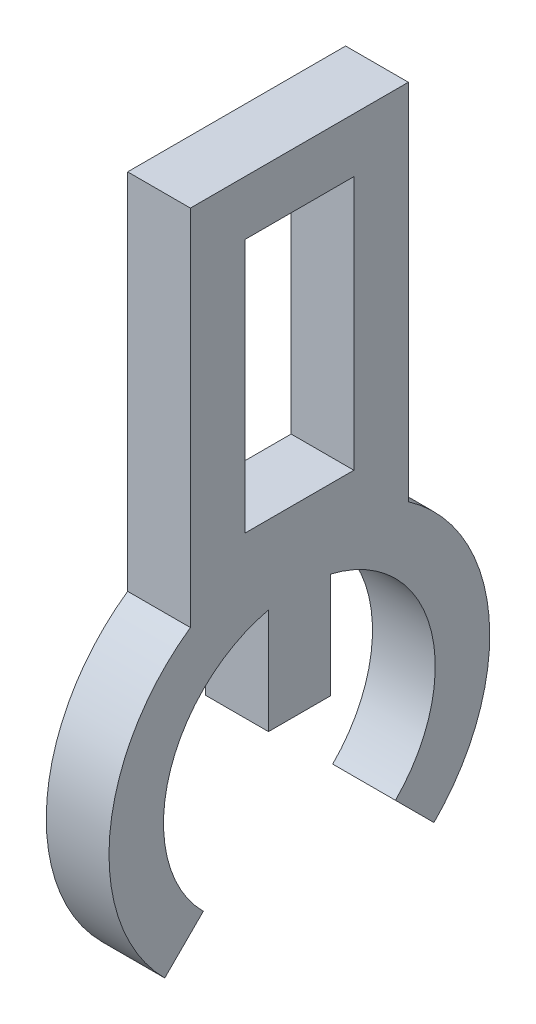
SolidWorks part; units mm, degrees
ref_plane "Front Plane" through (0, 0, 0) normal (0, 0, 1) x (1, 0, 0)
ref_plane "Top Plane" through (0, 0, 0) normal (0, 1, 0) x (1, 0, 0)
ref_plane "Right Plane" through (0, 0, 0) normal (1, 0, 0) x (0, 0, -1)
sketch "Sketch1" plane through (0, 0, 0) normal (1, 0, 0) x (0, 0, -1)
  line L0 (-2.6446, -2.6446) -> (2.6446, -2.6446) construction
  line L1 (-2.6446, -2.6446) -> (-3.7052, -3.7052)
  line L2 (3.7052, -3.7052) -> (2.6446, -2.6446)
  line L3 (0, 0) -> (0, 6.3411) construction
  line L4 (-1.5, 12.7962) -> (-1.5, 5.7962)
  line L5 (-3, 14.2962) -> (3, 14.2962)
  line L6 (-3, 14.2962) -> (-3, 4.2962)
  line L7 (-3, 4.2962) -> (3, 4.2962)
  line L8 (3, 14.2962) -> (3, 4.2962)
  line L9 (-3, 14.2962) -> (3, 4.2962) construction
  line L10 (-3, 4.2962) -> (3, 14.2962) construction
  line L11 (-1.5, 5.7962) -> (1.5, 5.7962)
  line L12 (1.5, 12.7962) -> (1.5, 5.7962)
  line L13 (-1.5, 12.7962) -> (1.5, 12.7962)
  line L15 (0.85, 3.74) -> (-0.85, 3.74)
  line L16 (0.85, 3.74) -> (0.85, 0.74)
  line L17 (0.85, 0.74) -> (-0.85, 0.74)
  line L18 (-0.85, 3.74) -> (-0.85, 0.74)
  line L19 (0.85, 3.74) -> (-0.85, 0.74) construction
  line L20 (0.85, 0.74) -> (-0.85, 3.74) construction
  arc A0 (-2.6446, -2.6446) -> (2.6446, -2.6446) centre (0, 0) cw
  arc A1 (-3.7052, -3.7052) -> (0, 5.24) centre (0, 0) cw
  arc A2 (0, 5.24) -> (3.7052, -3.7052) centre (0, 0) cw
  arc A3 (-3.7052, -3.7052) -> (3.7052, -3.7052) centre (0, 0) cw construction
  point P8 (0, 9.2962)
  point P12 (0, 3.74)
  point P20 (0, 2.24)
  dimension "D1" = 3.74
  dimension "D3" = 1.5
  dimension "D6" = 1.5
  dimension "D8" = 3
  dimension "D2" = 90
  dimension "D4" = 10
  dimension "D5" = 6
  dimension "D7" = 1.7
extrude "Boss-Extrude1" add sketch "Sketch1" along normal blind 1.7272 contours A1 L1 A0 L2 A2 | A1 | A2 A1 L7 | A0 L18 L17 L16 | L18 A0 L15 | L15 A0 L16 region at (0, -3.0817, 3.2681) region at (0, 2.2239, 0) region at (0, 3.7107, 0.6381) region at (0, 4.6768, 0) region at (0, 9.2962, 2.8834) region at (0, 3.7107, -0.6381)
